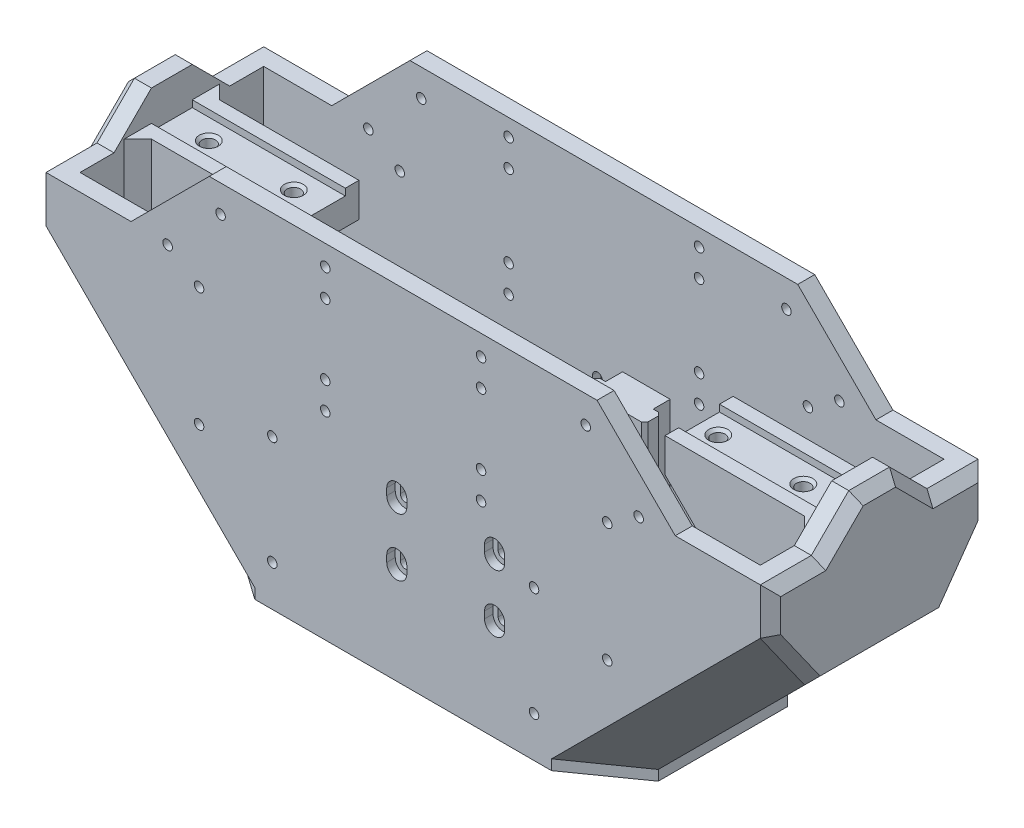
SolidWorks part; units mm, degrees
ref_plane "Front Plane" through (0, 0, 0) normal (0, 0, 1) x (1, 0, 0)
ref_plane "Top Plane" through (0, 0, 0) normal (0, 1, 0) x (1, 0, 0)
ref_plane "Right Plane" through (0, 0, 0) normal (1, 0, 0) x (0, 0, -1)
sketch "Sketch1" plane through (0, 0, 0) normal (0, 1, 0) x (1, 0, 0)
  line L1 (-100, -27) -> (100, -27)
  line L2 (-100, -27) -> (-100, 27)
  line L3 (-100, 27) -> (100, 27)
  line L4 (100, -27) -> (100, 27)
  line L5 (-100, -27) -> (100, 27) construction
  line L6 (-100, 27) -> (100, -27) construction
  point P0 (0, 0)
  dimension "D1" = 200
  dimension "D2" = 54
extrude "Boss-Extrude1" add sketch "Sketch1" along normal blind 70
shell "Shell1" thickness 5 removed face at (0, 70, 0) outward yes
sketch "Sketch2" plane through (105, 0, 0) normal (1, 0, 0) x (0, 0, -1)
  line L0 (-17, 70) -> (-6, 81)
  line L1 (-32, 70) -> (32, 70) construction
  line L2 (-6, 81) -> (6, 81)
  line L3 (6, 81) -> (17, 70)
  line L4 (17, 70) -> (-17, 70)
  line L5 (0, 81) -> (0, 75) construction
  dimension "D1" = 11
  dimension "D2" = 45
  dimension "D3" = 45
  dimension "D4" = 12
extrude "Boss-Extrude2" add sketch "Sketch2" against normal blind 5
sketch "Sketch4" plane through (0, 0, -32) normal (0, 0, -1) x (-1, 0, 0)
  line L0 (-80, 70) -> (-57, 93)
  line L1 (-105, 70) -> (105, 70) construction
  line L2 (-57, 93) -> (57, 93)
  line L3 (57, 93) -> (80, 70)
  line L4 (80, 70) -> (-80, 70)
  line L5 (0, 93) -> (0, 70) construction
  line L6 (-105, 70) -> (-105, -5) construction
  dimension "D1" = 23
  dimension "D2" = 25
  dimension "D3" = 45
extrude "Boss-Extrude3" add sketch "Sketch4" against normal blind 5
sketch "Sketch3" plane through (0, 0, -32) normal (0, 0, -1) x (-1, 0, 0)
  line L1 (-28, 56) -> (28, 56) construction
  line L2 (-28, 56) -> (-28, 88) construction
  line L3 (-28, 88) -> (28, 88) construction
  line L4 (28, 56) -> (28, 88) construction
  line L5 (-28, 56) -> (28, 88) construction
  line L6 (-28, 88) -> (28, 56) construction
  line L7 (57, 93) -> (-57, 93) construction
  circle A0 centre (-28, 88) radius 1.4
  circle A1 centre (-28, 56) radius 1.4
  circle A2 centre (28, 88) radius 1.4
  circle A3 centre (28, 56) radius 1.4
  point P0 (0, 72)
  dimension "D1" = 2.8
  dimension "D2" = 56
  dimension "D3" = 32
  dimension "D4" = 5
extrude "Cut-Extrude1" cut sketch "Sketch3" against normal blind 6
mirror "Mirror4" about plane through (0, 0, 0) normal (0, 0, 1) of "Boss-Extrude3"
mirror "Mirror5" about plane through (0, 0, 0) normal (1, 0, 0) of "Boss-Extrude2"
sketch "Sketch5" plane through (0, 0, 0) normal (0, 0, 1) x (1, 0, 0)
  line L0 (-100, 70) -> (-55, 70)
  line L1 (-55, 70) -> (-55, 62)
  line L2 (-55, 62) -> (-100, 17)
  line L4 (-100, 17) -> (-100, 70)
  line L5 (-100, 81) -> (-100, 70) construction
  line L6 (-105, 70) -> (-80, 70) construction
  dimension "D1" = 45
  dimension "D2" = 8
  dimension "D3" = 45
extrude "Boss-Extrude4" add sketch "Sketch5" along normal mid plane 20
sketch "Sketch9" plane through (0, 70, 0) normal (0, 1, 0) x (1, 0, 0)
  line L4 (-55, 10) -> (-100, 10)
  line L5 (-100, 10) -> (-100, -10)
  line L6 (-100, -10) -> (-55, -10)
  line L7 (-55, -10) -> (-55, 10)
  line L8 (-55, 10) -> (-100, 10)
  line L10 (-100, -10) -> (-55, -10)
  line L11 (-55, -10) -> (-55, 10)
  line L13 (-100, 10) -> (-100, -10)
  dimension "D1" = 0
extrude "Boss-Extrude6" add sketch "Sketch9" along normal blind 2
sketch "Sketch10" plane through (-100, 0, 0) normal (1, 0, 0) x (0, 0, -1)
  line L0 (-10, 72) -> (10, 72) construction
  line L1 (-6, 72) -> (6, 72)
  line L2 (-6, 72) -> (-6, 70)
  line L3 (-6, 70) -> (6, 70)
  line L4 (6, 72) -> (6, 70)
  line L5 (-6, 72) -> (6, 70) construction
  line L6 (-6, 70) -> (6, 72) construction
  point P0 (0, 71)
  dimension "D1" = 2
  dimension "D2" = 12
extrude "Cut-Extrude2" cut sketch "Sketch10" along normal up to next
mirror "Mirror24" about plane through (0, 0, 0) normal (1, 0, 0) of "Boss-Extrude6", "Boss-Extrude4", "Cut-Extrude2"
chamfer "Chamfer3" distance 40 angle 45 2 edges at (100, 0, 0) (-100, 0, 0)
chamfer "Chamfer5" distance 43 angle 45 2 edges at (105, -5, 0) (-105, -5, 0)
chamfer "Chamfer11" distance 10 angle 45 4 edges at (80, 20, 27) (80, 20, -27) (-80, 20, -27) (-80, 20, 27)
chamfer "Chamfer12" distance 13 angle 45 4 edges at (83.5, 16.5, -32) (83.5, 16.5, 32) (-83.5, 16.5, -32) (-83.5, 16.5, 32)
chamfer "Chamfer13" distance 4 angle 45 4 edges at (-100, 56, 10) (-100, 56, -10) (100, 56, 10) (100, 56, -10)
sketch "Sketch16" plane through (105, 0, 0) normal (1, 0, 0) x (0, 0, -1)
  line L10 (-19, 38) -> (19, 38)
  line L11 (19, 38) -> (32, 56.3848)
  line L12 (32, 56.3848) -> (32, 70)
  line L13 (32, 70) -> (17, 70)
  line L14 (17, 70) -> (6, 81)
  line L15 (6, 81) -> (-6, 81)
  line L16 (-6, 81) -> (-17, 70)
  line L17 (-17, 70) -> (-32, 70)
  line L18 (-32, 70) -> (-32, 56.3848)
  line L19 (-32, 56.3848) -> (-19, 38)
  line L20 (-19, 38) -> (19, 38)
  line L21 (19, 38) -> (32, 56.3848)
  line L22 (32, 56.3848) -> (32, 70)
  line L23 (32, 70) -> (17, 70)
  line L24 (17, 70) -> (6, 81)
  line L25 (6, 81) -> (-6, 81)
  line L26 (-6, 81) -> (-17, 70)
  line L27 (-17, 70) -> (-32, 70)
  line L28 (-32, 70) -> (-32, 56.3848)
  line L29 (-32, 56.3848) -> (-19, 38)
  dimension "D1" = 0
extrude "Boss-Extrude10" add sketch "Sketch16" along normal blind 3
chamfer "Chamfer14" distance 3 angle 45 10 edges at (108, 63.1924, 32) (108, 70, 24.5) (108, 75.5, 11.5) (108, 81, 0) (108, 75.5, -11.5) (108, 70, -24.5) (108, 63.1924, -32) (108, 47.1924, -25.5) (108, 38, 0) (108, 47.1924, 25.5)
mirror "Mirror28" about plane through (0, 0, 0) normal (1, 0, 0) of "Chamfer14", "Boss-Extrude10"
sketch "Sketch17" plane through (0, 0, 0) normal (0, 1, 0) x (1, 0, 0)
  line L0 (-57, -27) -> (57, -27) construction
  line L1 (5.5, -27) -> (19.5, -27)
  line L2 (5.5, -27) -> (5.5, -22)
  line L3 (5.5, -22) -> (19.5, -22)
  line L4 (19.5, -27) -> (19.5, -22)
  line L5 (5.5, -27) -> (19.5, -22) construction
  line L6 (5.5, -22) -> (19.5, -27) construction
  line L7 (3, -22) -> (22, -22)
  line L8 (3, -22) -> (3, -17)
  line L9 (3, -17) -> (22, -17)
  line L10 (22, -22) -> (22, -17)
  line L11 (3, -22) -> (22, -17) construction
  line L12 (3, -17) -> (22, -22) construction
  point P0 (12.5, -24.5)
  point P5 (12.5, -19.5)
  line M10 (-45.8579, -27) -> (45.8579, -27)
  dimension "D1" = 19
  dimension "D2" = 14
  dimension "D3" = 5
  dimension "D4" = 12.5
extrude "Boss-Extrude11" add sketch "Sketch17" along normal blind 45 contours L7 L10 L9 L8 L3 | L4 L3 L2 M10 region at (12.5, 0, 24.5) region at (12.5, 0, 19.5)
sketch "Sketch20" plane through (0, 0, 0) normal (0, 1, 0) x (1, 0, 0)
  line L0 (22, -22) -> (22, -17) construction
  line L1 (3, -17) -> (22, -17)
  line L2 (3, -17) -> (3, -12)
  line L3 (3, -12) -> (22, -12)
  line L4 (22, -17) -> (22, -12)
  dimension "D1" = 5
extrude "Boss-Extrude14" add sketch "Sketch20" along normal blind 8
mirror "Mirror29" about plane through (0, 0, 0) normal (0, 0, 1) of "Boss-Extrude14", "Boss-Extrude11"
sketch "Sketch22" plane through (0, 0, -27) normal (0, 0, 1) x (1, 0, 0)
  line L0 (5.5, 0) -> (-45.8579, 0) construction
  line L1 (-1.875, 21.8) -> (26.875, 21.8) construction
  line L2 (-1.875, 21.8) -> (-1.875, 38.8) construction
  line L3 (-1.875, 38.8) -> (26.875, 38.8) construction
  line L4 (26.875, 21.8) -> (26.875, 38.8) construction
  line L5 (-1.875, 21.8) -> (26.875, 38.8) construction
  line L6 (-1.875, 38.8) -> (26.875, 21.8) construction
  line L7 (3, 45) -> (22, 45) construction
  line L8 (-1.875, 37.8) -> (-1.875, 39.8) construction
  line L9 (-3.325, 37.8) -> (-3.325, 39.8)
  line L10 (-0.425, 37.8) -> (-0.425, 39.8)
  line L11 (12.5, 38.8) -> (12.5, 30.3) construction
  line L12 (12.5, 30.3) -> (-1.875, 30.3) construction
  line L13 (26.875, 37.8) -> (26.875, 39.8) construction
  line L14 (28.325, 37.8) -> (28.325, 39.8)
  line L15 (25.425, 37.8) -> (25.425, 39.8)
  line L16 (-1.875, 22.8) -> (-1.875, 20.8) construction
  line L17 (-3.325, 22.8) -> (-3.325, 20.8)
  line L18 (-0.425, 22.8) -> (-0.425, 20.8)
  line L19 (26.875, 22.8) -> (26.875, 20.8) construction
  line L20 (28.325, 22.8) -> (28.325, 20.8)
  line L21 (25.425, 22.8) -> (25.425, 20.8)
  arc A4 (-3.325, 37.8) -> (-0.425, 37.8) centre (-1.875, 37.8) ccw
  arc A5 (-0.425, 39.8) -> (-3.325, 39.8) centre (-1.875, 39.8) ccw
  arc A6 (28.325, 37.8) -> (25.425, 37.8) centre (26.875, 37.8) cw
  arc A7 (25.425, 39.8) -> (28.325, 39.8) centre (26.875, 39.8) cw
  arc A8 (-3.325, 22.8) -> (-0.425, 22.8) centre (-1.875, 22.8) cw
  arc A9 (-0.425, 20.8) -> (-3.325, 20.8) centre (-1.875, 20.8) cw
  arc A10 (28.325, 22.8) -> (25.425, 22.8) centre (26.875, 22.8) ccw
  arc A11 (25.425, 20.8) -> (28.325, 20.8) centre (26.875, 20.8) ccw
  point P0 (12.5, 30.3)
  point P7 (12.5, 45)
  point P11 (-1.875, 38.8)
  point P22 (26.875, 38.8)
  point P29 (-1.875, 21.8)
  point P36 (26.875, 21.8)
  dimension "D4" = 1.45
  dimension "D1" = 21.8
  dimension "D2" = 28.75
  dimension "D3" = 17
  dimension "D5" = 2
extrude "Cut-Extrude4" cut sketch "Sketch22" against normal blind 2.5
sketch "Sketch23" plane through (0, 0, -29.5) normal (0, 0, 1) x (1, 0, 0)
  line L6 (29.825, 37.8) -> (29.825, 39.8)
  line L7 (23.925, 39.8) -> (23.925, 37.8)
  line L8 (29.825, 37.8) -> (29.825, 39.8)
  line L9 (23.925, 39.8) -> (23.925, 37.8)
  line L12 (1.075, 37.8) -> (1.075, 39.8)
  line L13 (-4.825, 39.8) -> (-4.825, 37.8)
  line L14 (1.075, 37.8) -> (1.075, 39.8)
  line L15 (-4.825, 39.8) -> (-4.825, 37.8)
  line L18 (-4.825, 22.8) -> (-4.825, 20.8)
  line L19 (1.075, 20.8) -> (1.075, 22.8)
  line L20 (-4.825, 22.8) -> (-4.825, 20.8)
  line L21 (1.075, 20.8) -> (1.075, 22.8)
  line L24 (23.925, 22.8) -> (23.925, 20.8)
  line L25 (29.825, 20.8) -> (29.825, 22.8)
  line L26 (23.925, 22.8) -> (23.925, 20.8)
  line L27 (29.825, 20.8) -> (29.825, 22.8)
  arc A6 (23.925, 37.8) -> (29.825, 37.8) centre (26.875, 37.8) ccw
  arc A7 (29.825, 39.8) -> (23.925, 39.8) centre (26.875, 39.8) ccw
  arc A8 (23.925, 37.8) -> (29.825, 37.8) centre (26.875, 37.8) ccw
  arc A9 (29.825, 39.8) -> (23.925, 39.8) centre (26.875, 39.8) ccw
  arc A12 (-4.825, 37.8) -> (1.075, 37.8) centre (-1.875, 37.8) ccw
  arc A13 (1.075, 39.8) -> (-4.825, 39.8) centre (-1.875, 39.8) ccw
  arc A14 (-4.825, 37.8) -> (1.075, 37.8) centre (-1.875, 37.8) ccw
  arc A15 (1.075, 39.8) -> (-4.825, 39.8) centre (-1.875, 39.8) ccw
  arc A18 (1.075, 22.8) -> (-4.825, 22.8) centre (-1.875, 22.8) ccw
  arc A19 (-4.825, 20.8) -> (1.075, 20.8) centre (-1.875, 20.8) ccw
  arc A20 (1.075, 22.8) -> (-4.825, 22.8) centre (-1.875, 22.8) ccw
  arc A21 (-4.825, 20.8) -> (1.075, 20.8) centre (-1.875, 20.8) ccw
  arc A24 (29.825, 22.8) -> (23.925, 22.8) centre (26.875, 22.8) ccw
  arc A25 (23.925, 20.8) -> (29.825, 20.8) centre (26.875, 20.8) ccw
  arc A26 (29.825, 22.8) -> (23.925, 22.8) centre (26.875, 22.8) ccw
  arc A27 (23.925, 20.8) -> (29.825, 20.8) centre (26.875, 20.8) ccw
  dimension "D1" = 1.5
  dimension "D2" = 1.5
  dimension "D3" = 1.5
  dimension "D4" = 1.5
extrude "Cut-Extrude5" cut sketch "Sketch23" against normal up to next contours A8 L8 A9 L9 | A14 L14 A15 L15 | A20 L20 A21 L21 | A26 L26 A27 L27
mirror "Mirror30" about plane through (0, 0, 0) normal (0, 0, 1) of "Cut-Extrude5", "Cut-Extrude4"
sketch "Sketch24" plane through (30, -30, 0) normal (-0.7071, 0.7071, 0) x (0, 0, 1)
  line L0 (17, 42.4264) -> (-17, 42.4264) construction
  line L1 (-7.5, 47.4264) -> (7.5, 47.4264)
  line L2 (-7.5, 47.4264) -> (-7.5, 55.4264)
  line L3 (-7.5, 55.4264) -> (7.5, 55.4264)
  line L4 (7.5, 47.4264) -> (7.5, 55.4264)
  line L5 (-7.5, 47.4264) -> (7.5, 55.4264) construction
  line L6 (-7.5, 55.4264) -> (7.5, 47.4264) construction
  point P0 (0, 51.4264)
  dimension "D1" = 5
  dimension "D2" = 15
  dimension "D3" = 8
extrude "Cut-Extrude6" cut sketch "Sketch24" against normal up to next
chamfer "Chamfer18" distance 4 angle 45 4 edges at (22, 0, 17) (22, 0, -17) (3, 0, 17) (3, 0, -17)
chamfer "Chamfer19" distance 1 angle 45 8 edges at (3, 24.5, 22) (22, 26.5, 17) (22, 24.5, 22) (3, 26.5, 17) (22, 24.5, -22) (22, 26.5, -17) (3, 26.5, -17) (3, 24.5, -22)
chamfer "Chamfer20" distance 2 angle 45 4 edges at (65.2855, 1.7855, -7.5) (65.2855, 1.7855, 7.5) (70.9424, 7.4424, 7.5) (70.9424, 7.4424, -7.5)
sketch "Sketch25" plane through (0, -5, 0) normal (0, -1, 0) x (1, 0, 0)
  line L8 (-43.6152, -32) -> (43.6152, -32)
  line L9 (43.6152, -32) -> (62, -19)
  line L10 (62, -19) -> (62, 19)
  line L11 (62, 19) -> (43.6152, 32)
  line L12 (43.6152, 32) -> (-43.6152, 32)
  line L13 (-43.6152, 32) -> (-62, 19)
  line L14 (-62, 19) -> (-62, -19)
  line L15 (-62, -19) -> (-43.6152, -32)
  line L16 (-43.6152, -32) -> (43.6152, -32)
  line L17 (43.6152, -32) -> (62, -19)
  line L18 (62, -19) -> (62, 19)
  line L19 (62, 19) -> (43.6152, 32)
  line L20 (43.6152, 32) -> (-43.6152, 32)
  line L21 (-43.6152, 32) -> (-62, 19)
  line L22 (-62, 19) -> (-62, -19)
  line L23 (-62, -19) -> (-43.6152, -32)
  dimension "D1" = 0
extrude "Boss-Extrude15" add sketch "Sketch25" along normal blind 3
sketch "Sketch27" plane through (0, 0, 0) normal (0, 1, 0) x (1, 0, 0)
  line L0 (26, 12) -> (-1, 12) construction
  line L1 (-30, -12) -> (30, -12)
  line L2 (-30, -12) -> (-30, 12)
  line L3 (-30, 12) -> (30, 12)
  line L4 (30, -12) -> (30, 12)
  line L5 (22, -12) -> (3, -12) construction
  line L6 (-30, 12) -> (30, -12) construction
  point P8 (0, 0)
  dimension "D1" = 60
extrude "Cut-Extrude7" cut sketch "Sketch27" against normal up to next
chamfer "Chamfer21" distance 5 angle 45 4 edges at (-30, -4, -12) (30, -4, -12) (30, -4, 12) (-30, -4, 12)
sketch "Sketch28" plane through (0, -8, 0) normal (0, -1, 0) x (1, 0, 0)
  line L0 (62, 19) -> (43.6152, 32) construction
  line L1 (-52.8076, -25.5) -> (52.8076, -25.5) construction
  line L2 (-52.8076, -25.5) -> (-52.8076, 25.5) construction
  line L3 (-52.8076, 25.5) -> (52.8076, 25.5) construction
  line L4 (52.8076, -25.5) -> (52.8076, 25.5) construction
  line L5 (-52.8076, -25.5) -> (52.8076, 25.5) construction
  line L6 (-52.8076, 25.5) -> (52.8076, -25.5) construction
  circle A0 centre (-52.8076, 0) radius 2.75
  circle A1 centre (-52.8076, 15) radius 2.75
  circle A2 centre (-52.8076, -15) radius 2.75
  point P0 (0, 0)
  dimension "D1" = 5.5
  dimension "D2" = 15
  dimension "D3" = 15
extrude "Cut-Extrude8" cut sketch "Sketch28" against normal blind 6
mirror "Mirror31" about plane through (0, 0, 0) normal (1, 0, 0) of "Cut-Extrude8"
sketch "Sketch29" plane through (0, -8, 0) normal (0, -1, 0) x (1, 0, 0)
  line L0 (-54.9289, 24) -> (54.9289, 24) construction
  line L3 (43.6152, 32) -> (-43.6152, 32) construction
  line L4 (-43.6152, 32) -> (-62, 19) construction
  line L5 (62, 19) -> (43.6152, 32) construction
  circle A1 centre (0, 24) radius 2.75
  circle A2 centre (20, 24) radius 2.75
  circle A3 centre (40, 24) radius 2.75
  dimension "D1" = 5.5
  dimension "D3" = 20
  dimension "D4" = 8
  dimension "D2" = 3
extrude "Cut-Extrude9" cut sketch "Sketch29" against normal blind 6
mirror "Mirror32" about plane through (0, 0, 0) normal (1, 0, 0) of "Cut-Extrude9"
mirror "Mirror33" about plane through (0, 0, 0) normal (0, 0, 1) of "Mirror32"
sketch "Sketch32" plane through (0, -2, 0) normal (0, -1, 0) x (1, 0, 0)
  circle A0 centre (-40, 24) radius 1.9
  circle A1 centre (-52.8076, 15) radius 1.9
  circle A2 centre (-52.8076, 0) radius 1.9
  dimension "D1" = 3.8
extrude "Cut-Extrude11" cut sketch "Sketch32" against normal blind 2
mirror "Mirror34" about plane through (0, 0, 0) normal (0, 0, 1) of "Cut-Extrude11"
mirror "Mirror35" about plane through (0, 0, 0) normal (1, 0, 0) of "Mirror34"
sketch "Sketch33" plane through (0, 70, 0) normal (0, 1, 0) x (1, 0, 0)
  line L0 (-100, -6) -> (-100, 6) construction
  circle A0 centre (-89.15, 0) radius 2
  circle A1 centre (-64.15, 0) radius 2
  point P6 (0, 0)
  point P7 (0, 0)
  dimension "D1" = 25
  dimension "D2" = 10.85
  dimension "D3" = 4
extrude "Cut-Extrude12" cut sketch "Sketch33" against normal blind 6
sketch "Sketch34" plane through (0, 70, 0) normal (0, 1, 0) x (1, 0, 0)
  line L0 (100, 6) -> (100, -6) construction
  circle A0 centre (85.65, 0) radius 2
  circle A1 centre (60.65, 0) radius 2
  point P4 (0, 0)
  dimension "D1" = 4
  dimension "D2" = 25
  dimension "D3" = 14.35
extrude "Cut-Extrude13" cut sketch "Sketch34" against normal blind 6
sketch "Sketch35" plane through (0, 64, 0) normal (0, 1, 0) x (1, 0, 0)
  circle A0 centre (-89.15, 0) radius 1.4
  circle A1 centre (-64.15, 0) radius 1.4
  circle A2 centre (60.65, 0) radius 1.4
  circle A3 centre (85.65, 0) radius 1.4
  dimension "D1" = 2.8
extrude "Cut-Extrude14" cut sketch "Sketch35" against normal blind 6
pattern_linear "LPattern1" count 2 spacing 8 along (0, -1, 0) of "Cut-Extrude1"
sketch "Sketch36" plane through (0, 0, 32) normal (0, 0, 1) x (1, 0, 0)
  line L0 (-57, 93) -> (57, 93) construction
  line L1 (-22.9, 58.3) -> (22.9, 58.3) construction
  line L2 (-22.9, 58.3) -> (-22.9, 87) construction
  line L3 (-22.9, 87) -> (22.9, 87) construction
  line L4 (22.9, 58.3) -> (22.9, 87) construction
  line L5 (-22.9, 58.3) -> (22.9, 87) construction
  line L6 (-22.9, 87) -> (22.9, 58.3) construction
  circle A0 centre (-22.9, 87) radius 1.4
  circle A1 centre (22.9, 87) radius 1.4
  circle A2 centre (22.9, 58.3) radius 1.4
  circle A3 centre (-22.9, 58.3) radius 1.4
  point P0 (0, 72.65)
  point P9 (0, 0)
  point P11 (0, 71.0499)
  dimension "D1" = 2.8
  dimension "D2" = 45.8
  dimension "D3" = 28.7
  dimension "D4" = 6
extrude "Cut-Extrude15" cut sketch "Sketch36" against normal up to next
pattern_linear "LPattern2" count 2 spacing 8 along (0, -1, 0) of "Cut-Extrude15"
sketch "Sketch39" plane through (0, 0, -32) normal (0, 0, -1) x (-1, 0, 0)
  line L0 (-105, 56.3848) -> (-43.6152, -5) construction
  line L1 (-38.4731, 4) -> (38.4731, 4) construction
  line L2 (-38.4731, 4) -> (-38.4731, 36) construction
  line L3 (-38.4731, 36) -> (38.4731, 36) construction
  line L4 (38.4731, 4) -> (38.4731, 36) construction
  line L5 (-38.4731, 4) -> (38.4731, 36) construction
  line L6 (-38.4731, 36) -> (38.4731, 4) construction
  line L8 (43.6152, -8) -> (-43.6152, -8) construction
  circle A0 centre (-38.4731, 4) radius 1.4
  circle A1 centre (38.4731, 4) radius 1.4
  circle A2 centre (38.4731, 36) radius 1.4
  circle A3 centre (-38.4731, 36) radius 1.4
  point P0 (0, 20)
  dimension "D4" = 2.8
  dimension "D1" = 10
  dimension "D2" = 12
  dimension "D3" = 32
extrude "Cut-Extrude16" cut sketch "Sketch39" against normal up to next
sketch "Sketch40" plane through (0, 0, -32) normal (0, 0, -1) x (-1, 0, 0)
  line L1 (-60, 28.3553) -> (60, 28.3553) construction
  line L2 (-60, 28.3553) -> (-60, 63.3553) construction
  line L3 (-60, 63.3553) -> (60, 63.3553) construction
  line L4 (60, 28.3553) -> (60, 63.3553) construction
  line L5 (-60, 28.3553) -> (60, 63.3553) construction
  line L6 (-60, 63.3553) -> (60, 28.3553) construction
  line L9 (43.6152, -5) -> (105, 56.3848) construction
  circle A0 centre (-60, 63.3553) radius 1.4
  circle A1 centre (60, 63.3553) radius 1.4
  circle A2 centre (60, 28.3553) radius 1.4
  circle A3 centre (-60, 28.3553) radius 1.4
  point P0 (0, 45.8553)
  point P11 (74.8725, 62)
  point P13 (80.9289, 62)
  dimension "D4" = 2.8
  dimension "D3" = 12
  dimension "D1" = 120
  dimension "D2" = 35
extrude "Cut-Extrude17" cut sketch "Sketch40" against normal up to next
mirror "Mirror36" about plane through (0, 0, 0) normal (0, 0, 1) of "Cut-Extrude16", "Cut-Extrude17"
sketch "Sketch41" plane through (0, 0, -32) normal (0, 0, -1) x (-1, 0, 0)
  line L0 (-53.6863, 85) -> (-69.2426, 69.4437) construction
  line L2 (-57, 93) -> (-80, 70) construction
  line L4 (57, 93) -> (-57, 93) construction
  circle A1 centre (-69.2426, 69.4437) radius 1.4
  circle A2 centre (-53.6863, 85) radius 1.4
  point P7 (0, 0)
  point P9 (-53.9819, 84.7044)
  point P10 (0, 0)
  dimension "D2" = 2.8
  dimension "D3" = 22
  dimension "D4" = 8
  dimension "D1" = 8
extrude "Cut-Extrude18" cut sketch "Sketch41" against normal up to next
mirror "Mirror37" about plane through (0, 0, 0) normal (1, 0, 0) of "Cut-Extrude18"
mirror "Mirror38" about plane through (0, 0, 0) normal (0, 0, 1) of "Mirror37"
sketch "Sketch43" plane through (-33.5, -33.5, 0) normal (-0.7071, -0.7071, 0) x (0, 0, 1)
  line L1 (-12, 49.7107) -> (12, 49.7107) construction
  line L2 (-12, 49.7107) -> (-12, 91.7107) construction
  line L3 (-12, 91.7107) -> (12, 91.7107) construction
  line L4 (12, 49.7107) -> (12, 91.7107) construction
  line L5 (-12, 49.7107) -> (12, 91.7107) construction
  line L6 (-12, 91.7107) -> (12, 49.7107) construction
  line L10 (-19, 101.1163) -> (-19, 40.3051) construction
  circle A0 centre (-12, 91.7107) radius 1.4
  circle A1 centre (12, 91.7107) radius 1.4
  circle A2 centre (12, 49.7107) radius 1.4
  circle A3 centre (-12, 49.7107) radius 1.4
  point P0 (0, 70.7107)
  point P6 (-19, 70.7107)
  dimension "D3" = 2.8
  dimension "D1" = 42
  dimension "D2" = 24
extrude "Cut-Extrude19" cut sketch "Sketch43" against normal up to next
chamfer "Chamfer22" distance 0.8 angle 45 4 edges at (85.65, 70, 2) (60.65, 70, 2) (-64.15, 70, 2) (-89.15, 70, 2)
chamfer "Chamfer23" distance 0.8 angle 45 17 edges at (-20, -8, 21.25) (-20, -2, 21.25) (0, -8, 21.25) (-40, -8, 21.25) (-52.8076, -8, 12.25) (-52.8076, -8, -2.75) (-52.8076, -8, -17.75) (-40, -8, -21.25) (-20, -8, -21.25) (0, -8, -21.25) (20, -8, 21.25) (40, -8, 21.25) (52.8076, -8, 12.25) (52.8076, -8, -2.75) (20, -8, -21.25) (40, -8, -21.25) (52.8076, -8, -17.75)
